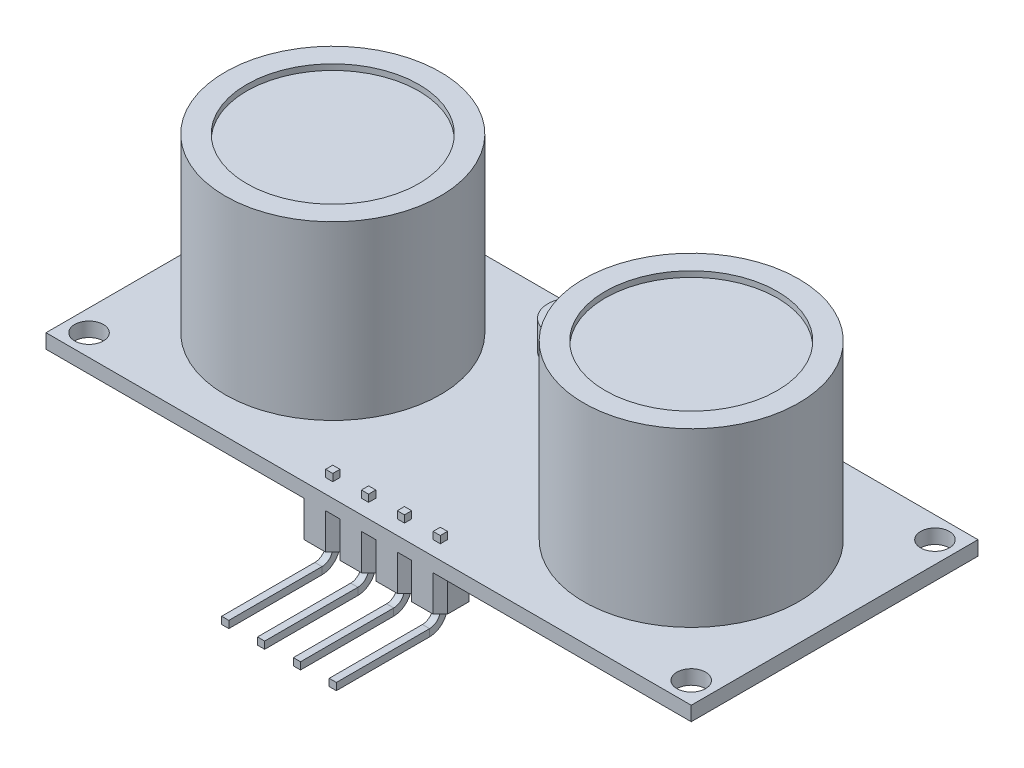
SolidWorks part; units mm, degrees
ref_plane "Front Plane" through (0, 0, 0) normal (0, 0, 1) x (1, 0, 0)
ref_plane "Top Plane" through (0, 0, 0) normal (0, 1, 0) x (1, 0, 0)
ref_plane "Right Plane" through (0, 0, 0) normal (1, 0, 0) x (0, 0, -1)
sketch "Sketch1" plane through (0, 0, 0) normal (0, 1, 0) x (1, 0, 0)
  line L0 (0, 29.7918) -> (0, -23.0028) construction
  line L1 (-22.5, 10) -> (22.5, 10)
  line L2 (-22.5, 10) -> (-22.5, -10)
  line L3 (-22.5, -10) -> (22.5, -10)
  line L4 (22.5, 10) -> (22.5, -10)
  line L5 (-63.4598, 0) -> (-61.463, 0) construction
  point P6 (-22.5, 0)
  point P7 (0, 10)
  dimension "D1" = 45
  dimension "D2" = 20
extrude "Boss-Extrude1" add sketch "Sketch1" along normal blind 1
sketch "Sketch2" plane through (0, 1, 0) normal (0, 1, 0) x (1, 0, 0)
  line L0 (0, 57.8605) -> (0, -50.5623) construction
  line L1 (-96.7789, 0) -> (123.3092, 0) construction
  circle A0 centre (-12.5, 0) radius 7.5
  circle A1 centre (-12.5, 0) radius 6
  circle A2 centre (12.5, 0) radius 6
  circle A3 centre (12.5, 0) radius 7.5
  dimension "D1" = 15
  dimension "D2" = 12.5
  dimension "D3" = 12
extrude "Boss-Extrude2" add sketch "Sketch2" along normal blind 12
sketch "Sketch3" plane through (0, 1, 0) normal (0, 1, 0) x (1, 0, 0)
  line L0 (0, 52.6424) -> (0, 3.5257) construction
  line L1 (-3, 9) -> (3, 9)
  line L3 (-3, 5.5) -> (3, 5.5)
  line L5 (22.5, 10) -> (-22.5, 10) construction
  arc A0 (-3, 9) -> (-3, 5.5) centre (-3, 7.25) ccw
  arc A1 (3, 9) -> (3, 5.5) centre (3, 7.25) cw
  point P8 (0, 9)
  dimension "D3" = 1
  dimension "D1" = 3.5
  dimension "D2" = 6
extrude "Boss-Extrude3" add sketch "Sketch3" along normal blind 2
sketch "Sketch4" plane through (0, 13, 0) normal (0, 1, 0) x (1, 0, 0)
  circle A0 centre (-12.5, 0) radius 6 construction
  circle A1 centre (-12.5, 0) radius 6
  circle A2 centre (12.5, 0) radius 6 construction
  circle A3 centre (12.5, 0) radius 6
extrude "Boss-Extrude4" add sketch "Sketch4" along normal blind 0.1 from offset 0.5 offset against normal yes
ref_plane "Plane1" through (3.75, 0, 0) normal (1, 0, 0) x (0, 0, -1)
sketch "Sketch8" plane through (3.75, 0, 0) normal (1, 0, 0) x (0, 0, -1)
  line L0 (-8.75, 0) -> (-8.75, -3)
  line L1 (-9.75, -4) -> (-16.25, -4)
  line L2 (-10, 1) -> (-10, 0) construction
  line L3 (-10, 0) -> (10, 0) construction
  arc A0 (-8.75, -3) -> (-9.75, -4) centre (-9.75, -3) cw
  point P11 (-8.75, -4)
  dimension "D4" = 1
  dimension "D1" = 4
  dimension "D2" = 7.5
  dimension "D3" = 1.25
sketch "Sketch9" plane through (0, 0, 0) normal (0, -1, 0) x (1, 0, 0)
  line L1 (3.5, 8.5) -> (4, 8.5)
  line L2 (3.5, 8.5) -> (3.5, 9)
  line L3 (3.5, 9) -> (4, 9)
  line L4 (4, 8.5) -> (4, 9)
  line L5 (3.5, 8.5) -> (4, 9) construction
  line L6 (3.5, 9) -> (4, 8.5) construction
  point P0 (3.75, 8.75)
  dimension "D1" = 0.5
  dimension "D2" = 0.5
sweep "Sweep1" add profiles "Sketch9" path "Sketch8"
extrude "Boss-Extrude7" add sketch "Sketch9<2>" against normal blind 1.5
sketch "Sketch9<2>" plane through (0, 0, 0) normal (0, -1, 0) x (1, 0, 0) same geometry as "Sketch9"
pattern_linear "LPattern5" count 4 spacing 2.5 along (-1, 0, 0) of face at (3.75, -4.25, 13) of face at (4, -4, 13) of face at (4, -3.6036, 9.1464) of face at (4, -1.5, 8.75) of face at (3.75, -1.5, 8.5) of face at (3.75, -3.7544, 8.9956) of face at (3.5, -1.5, 8.75) of face at (3.5, -3.6036, 9.1464) of face at (3.75, -1.5, 9) of face at (3.75, -3.4527, 9.2973) of face at (3.75, -3.75, 13) of face at (3.75, -4, 16.25) of face at (3.5, -4, 13) of face at (4, 1.25, 8.75) of face at (3.75, 1.25, 9) of face at (3.75, 1.5, 8.75) of face at (3.5, 1.25, 8.75) of face at (3.75, 1.25, 8.5)
sketch "Sketch11" plane through (0, 0, 0) normal (0, -1, 0) x (1, 0, 0)
  line L0 (3.75, -9.4875) -> (3.75, 9.4875) construction
  line L1 (3, 7.5) -> (4.5, 7.5)
  line L3 (3, 10) -> (4.5, 10)
  line L4 (5, 8) -> (5, 9.5)
  line L5 (2.5, 7.5) -> (5, 10) construction
  line L6 (2.5, 10) -> (5, 7.5) construction
  line L7 (-22.5, 10) -> (22.5, 10) construction
  line L8 (4.5, 10) -> (5, 9.5)
  line L9 (2.5, 9.5) -> (3, 10)
  line L10 (2.5, 8) -> (3, 7.5)
  line L11 (4.5, 7.5) -> (5, 8)
  line L12 (0.5, 7.5) -> (2, 7.5)
  line L14 (0.5, 10) -> (2, 10)
  line L16 (2, 10) -> (2.5, 9.5)
  line L17 (0, 9.5) -> (0.5, 10)
  line L18 (0, 8) -> (0.5, 7.5)
  line L19 (2, 7.5) -> (2.5, 8)
  line L20 (0, 7.5) -> (2.5, 10) construction
  line L21 (0, 10) -> (2.5, 7.5) construction
  line L22 (-2, 7.5) -> (-0.5, 7.5)
  line L24 (-2, 10) -> (-0.5, 10)
  line L26 (-0.5, 10) -> (0, 9.5)
  line L27 (-2.5, 9.5) -> (-2, 10)
  line L28 (-2.5, 8) -> (-2, 7.5)
  line L29 (-0.5, 7.5) -> (0, 8)
  line L30 (-2.5, 7.5) -> (0, 10) construction
  line L31 (-2.5, 10) -> (0, 7.5) construction
  line L32 (-4.5, 7.5) -> (-3, 7.5)
  line L33 (-5, 8) -> (-5, 9.5)
  line L34 (-4.5, 10) -> (-3, 10)
  line L36 (-3, 10) -> (-2.5, 9.5)
  line L37 (-5, 9.5) -> (-4.5, 10)
  line L38 (-5, 8) -> (-4.5, 7.5)
  line L39 (-3, 7.5) -> (-2.5, 8)
  line L40 (-5, 7.5) -> (-2.5, 10) construction
  line L41 (-5, 10) -> (-2.5, 7.5) construction
  line L42 (-2.5, 8) -> (-2.5, 9.5) [skipped]
  line L45 (0, 8) -> (0, 9.5) [skipped]
  line L46 (2.5, 8) -> (2.5, 9.5) [skipped]
  point P0 (3.75, 8.75)
  point P19 (1.25, 8.75)
  point P32 (-1.25, 8.75)
  point P45 (-3.75, 8.75)
  dimension "D1" = 2.5
  dimension "D2" = 2.5
  dimension "D3" = 4
extrude "Boss-Extrude6" add sketch "Sketch11" along normal blind 2.5
sketch "Sketch12" plane through (0, 0, 0) normal (0, -1, 0) x (1, 0, 0)
  line L0 (-22.5, 10) -> (-4.5, 10) construction
  line L1 (-22.5, -10) -> (-22.5, 10) construction
  line L2 (0, 24.2846) -> (0, 29.3303) construction
  line L3 (-59.3171, 0) -> (-52.3888, 0) construction
  circle A0 centre (-21, 8.5) radius 1
  circle A1 centre (-21, -8.5) radius 1
  circle A2 centre (21, -8.5) radius 1
  circle A3 centre (21, 8.5) radius 1
  dimension "D1" = 2
  dimension "D2" = 1.5
  dimension "D3" = 1.5
extrude "Cut-Extrude4" cut sketch "Sketch12" against normal blind 1.5
